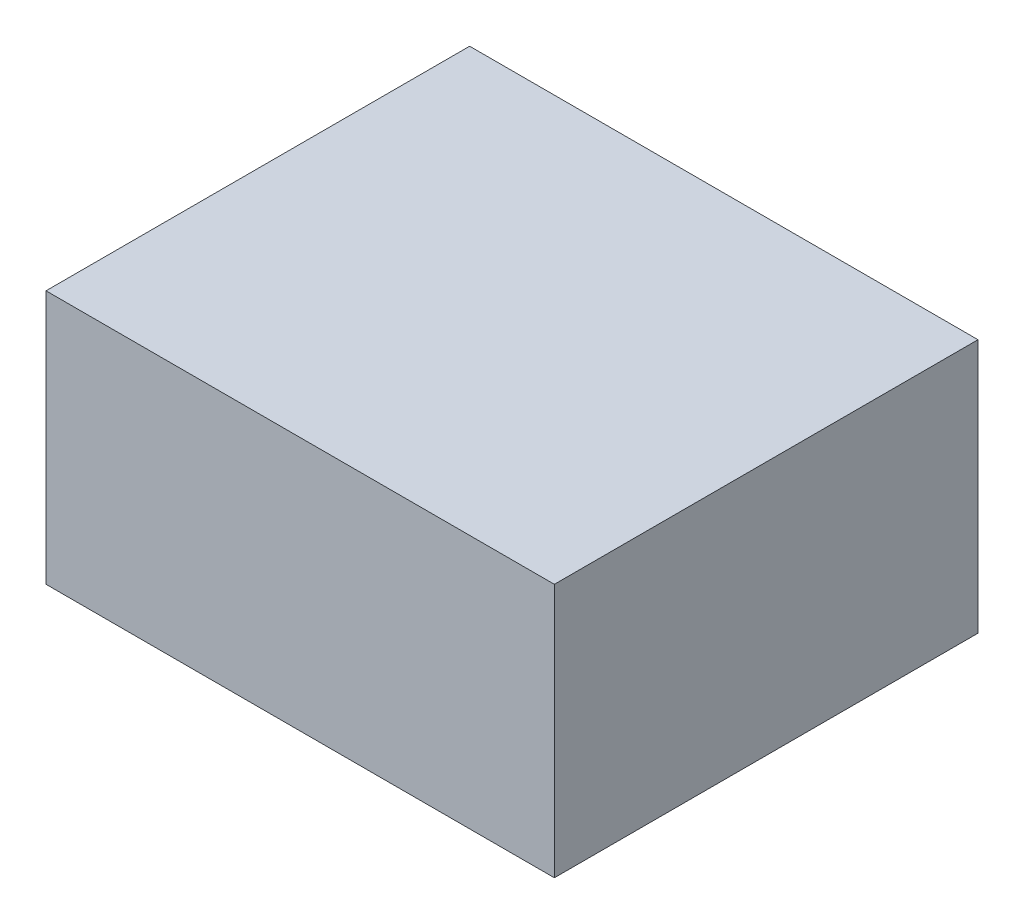
SolidWorks part; units mm, degrees
ref_plane "Front Plane" through (0, 0, 0) normal (0, 0, 1) x (1, 0, 0)
ref_plane "Top Plane" through (0, 0, 0) normal (0, 1, 0) x (1, 0, 0)
ref_plane "Right Plane" through (0, 0, 0) normal (1, 0, 0) x (0, 0, -1)
sketch "Sketch1" plane through (0, 0, 0) normal (0, 1, 0) x (1, 0, 0)
  line L1 (-76.2, -63.5) -> (76.2, -63.5)
  line L2 (-76.2, -63.5) -> (-76.2, 63.5)
  line L3 (-76.2, 63.5) -> (76.2, 63.5)
  line L4 (76.2, -63.5) -> (76.2, 63.5)
  line L5 (-76.2, -63.5) -> (76.2, 63.5) construction
  line L6 (-76.2, 63.5) -> (76.2, -63.5) construction
  point P0 (0, 0)
  dimension "D1" = 127
  dimension "D2" = 152.4
extrude "Boss-Extrude1" add sketch "Sketch1" along normal blind 76.2
